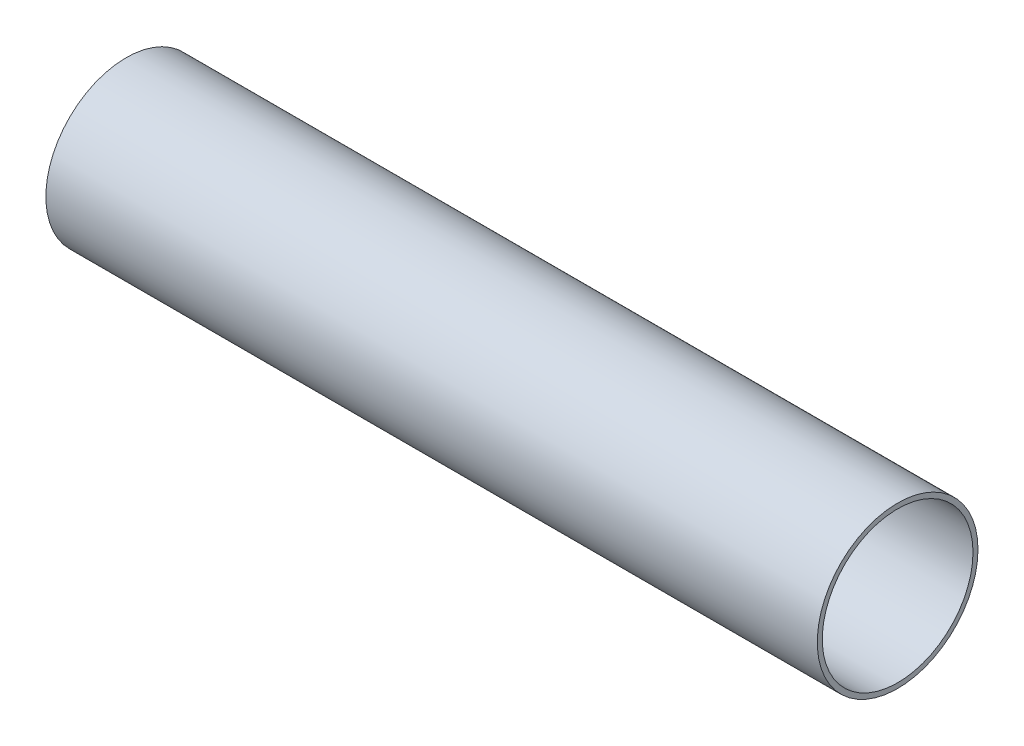
SolidWorks part; units mm, degrees
ref_plane "Front Plane" through (0, 0, 0) normal (0, 0, 1) x (1, 0, 0)
ref_plane "Top Plane" through (0, 0, 0) normal (0, 1, 0) x (1, 0, 0)
ref_plane "Right Plane" through (0, 0, 0) normal (1, 0, 0) x (0, 0, -1)
sketch "Sketch1" plane through (0, 0, 0) normal (1, 0, 0) x (0, 0, -1)
  circle A0 centre (0, 0) radius 14.2875
  circle A1 centre (0, 0) radius 13.3985
extrude "Boss-Extrude1" add sketch "Sketch1" along normal mid plane 137.16
